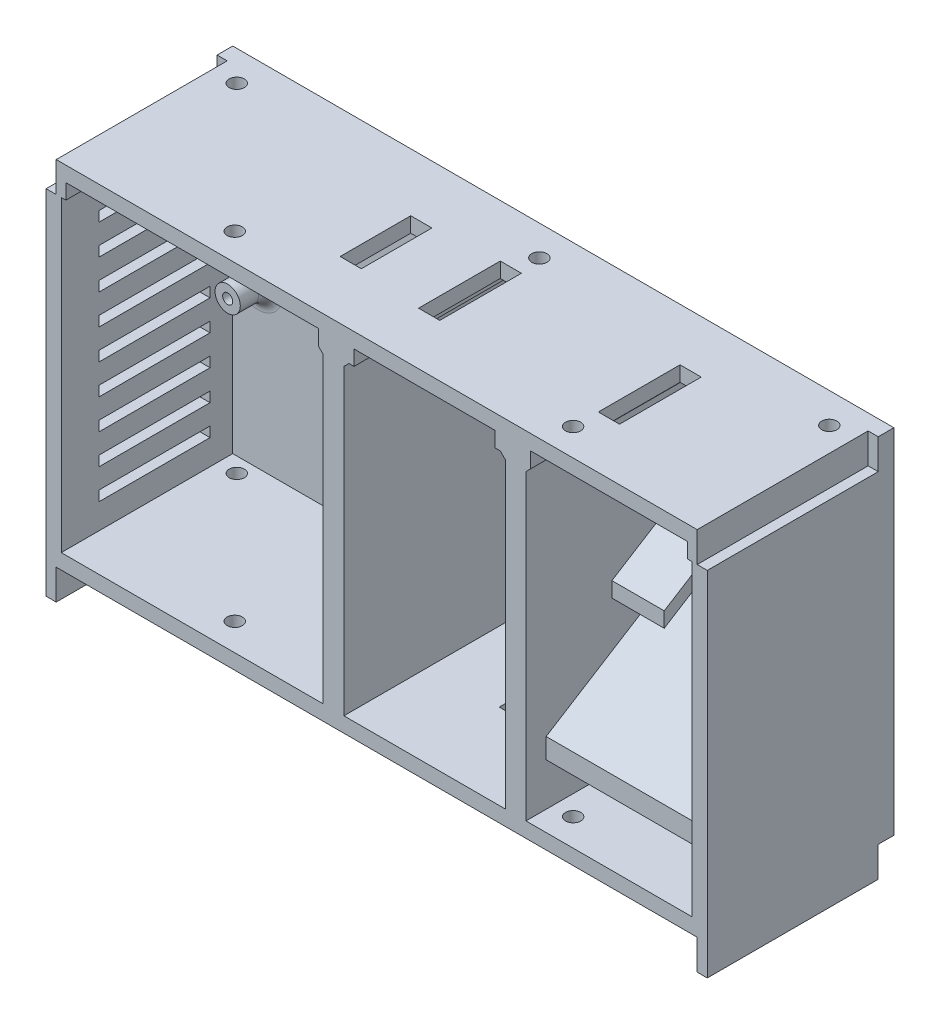
SolidWorks part; units mm, degrees
material "ABS"
ref_plane "Alzado" through (0, 0, 0) normal (0, 0, 1) x (1, 0, 0)
ref_plane "Planta" through (0, 0, 0) normal (0, 1, 0) x (1, 0, 0)
ref_plane "Vista lateral" through (0, 0, 0) normal (1, 0, 0) x (0, 0, -1)
sketch "Croquis1" plane through (0, 0, 0) normal (0, 0, 1) x (1, 0, 0)
  line L0 (0, 0) -> (2, 0)
  line L1 (2, 0) -> (2, 6)
  line L2 (55, 0) -> (55, 6)
  line L3 (55, 6) -> (2, 6)
  line L4 (56, 0) -> (56, 6)
  line L5 (56, 6) -> (58, 6)
  line L6 (58, 6) -> (58, 0)
  line L7 (58, 0) -> (59, 0)
  line L8 (59, 0) -> (59, 6)
  line L9 (91.1, 0) -> (91.1, 6)
  line L10 (59, 6) -> (91.1, 6)
  line L11 (92.1, 0) -> (92.1, 6)
  line L12 (92.1, 6) -> (94.1, 6)
  line L13 (94.1, 6) -> (94.1, 0)
  line L14 (95.1, 0) -> (95.1, 6)
  line L15 (129.1, 0) -> (129.1, 6)
  line L16 (129.1, 6) -> (95.1, 6)
  line L17 (0, 0) -> (0, -64)
  line L18 (0, -64) -> (131.1, -64)
  line L19 (131.1, -64) -> (131.1, 0)
  line L20 (55, 0) -> (56, 0)
  line L21 (58, 0) -> (59, 0)
  line L22 (129.1, 0) -> (131.1, 0)
  line L23 (94.1, 0) -> (95.1, 0)
  line L24 (91.1, 0) -> (92.1, 0)
  line L25 (2, 0) -> (129.1, 0)
  line L26 (55, 6) -> (56, 6)
  line L27 (58, 6) -> (59, 6)
  line L28 (91.1, 6) -> (92.1, 6)
  line L29 (94.1, 6) -> (95.1, 6)
  point P3 (2, 0)
  point P4 (129.1, 0)
  point P5 (55, 0)
  point P10 (56, 0)
  point P11 (58, 0)
  point P12 (59, 0)
  point P15 (91.1, 0)
  point P22 (92.1, 0)
  point P23 (94.1, 0)
  point P24 (95.1, 0)
  dimension "D1" = 131.1
  dimension "D2" = 2
  dimension "D3" = 2
  dimension "D4" = 55
  dimension "D5" = 6
  dimension "D6" = 1
  dimension "D7" = 2
  dimension "D8" = 1
  dimension "D9" = 32.1
  dimension "D10" = 1
  dimension "D11" = 2
  dimension "D12" = 1
  dimension "D13" = 64
extrude "Saliente-Extruir1" add sketch "Croquis1" along normal blind 34 contours L8 L25 L9 L10 | L1 L25 L2 L3 | L14 L25 L15 L16 | L11 L25 L13 L12 | L4 L25 L6 L5 | L26 L2 L20 L4 | L27 L6 L7 L8 | L29 L13 L23 L14 | L28 L9 L24 L11 region at (28.5, 3, 0) region at (55.5, 3, 0) region at (57, 3, 0) region at (58.5, 3, 0) region at (112.1, 3, 0) region at (75.05, 3, 0) region at (94.6, 3, 0) region at (91.6, 3, 0) region at (93.1, 3, 0)
sketch "Croquis2" plane through (0, 0, 0) normal (0, 0, 1) x (1, 0, 0)
  line L1 (2, -64) -> (129.1, -64)
  line L3 (129.1, 0) -> (2, 0)
  line L5 (129.1, 0) -> (131.1, 0)
  line L7 (129.1, -64) -> (131.1, -64)
  line L8 (131.1, 0) -> (131.1, -64)
  line L9 (2, -64) -> (0, -64)
  line L11 (2, 0) -> (0, 0)
  line L12 (0, -64) -> (0, 0)
  dimension "D1" = 64
  dimension "D2" = 2
  dimension "D3" = 2
extrude "Saliente-Extruir2" add sketch "Croquis2" along normal blind 3
sketch "Croquis3" plane through (0, 0, 3) normal (0, 0, 1) x (1, 0, 0)
  line L0 (0, -64) -> (131.1, -64) construction
  line L1 (131.1, 0) -> (128.1, 0)
  line L2 (131.1, 0) -> (131.1, -64)
  line L3 (131.1, -64) -> (128.1, -64)
  line L4 (128.1, 0) -> (128.1, -61)
  line L6 (0, 0) -> (3, 0)
  line L7 (0, 0) -> (0, -64)
  line L8 (0, -64) -> (3, -64)
  line L9 (3, 0) -> (3, -61)
  line L10 (3, -64) -> (128.1, -64)
  line L12 (3, -61) -> (128.1, -61)
  dimension "D1" = 3
  dimension "D2" = 3
  dimension "D3" = 3
extrude "Saliente-Extruir3" add sketch "Croquis3" along normal up to vertex (31 mm away) up to point (129.1, 0, 34)
sketch "Croquis4" plane through (0, 0, 0) normal (0, 0, -1) x (-1, 0, 0)
  line L25 (-2, 6) -> (-129.1, 6)
  line L34 (-129.1, 6) -> (-129.1, 0)
  line L35 (-129.1, 0) -> (-131.1, 0)
  line L36 (-131.1, 0) -> (-131.1, -64)
  line L37 (-131.1, -64) -> (0, -64)
  line L38 (0, -64) -> (0, 0)
  line L39 (0, 0) -> (-2, 0)
  line L40 (-2, 0) -> (-2, 6)
  line L49 (-2, 6) -> (-129.1, 6)
  line L58 (-129.1, 6) -> (-129.1, 0)
  line L59 (-129.1, 0) -> (-131.1, 0)
  line L60 (-131.1, 0) -> (-131.1, -64)
  line L61 (-131.1, -64) -> (0, -64)
  line L62 (0, -64) -> (0, 0)
  line L63 (0, 0) -> (-2, 0)
  line L64 (-2, 0) -> (-2, 6)
  dimension "D1" = 0
extrude "Saliente-Extruir4" add sketch "Croquis4" along normal blind 3
sketch "Croquis5" plane through (0, 0, 3) normal (0, 0, 1) x (1, 0, 0)
  line L1 (128.1, -61) -> (3, -61) construction
  line L4 (0, -64) -> (0, 0) construction
  line L23 (54.95, 0.05) -> (59.05, 0.05)
  line L26 (128.1, 0) -> (3, 0) construction
  line L27 (54.95, 0.05) -> (54.95, -61)
  line L28 (59.05, 0.05) -> (59.05, -61)
  line L29 (91.05, 0.05) -> (95.15, 0.05)
  line L32 (196.65, 0) -> (-65.55, 0) construction
  line L33 (91.05, 0.05) -> (91.05, -61)
  line L34 (128.1, -61) -> (3, -61) construction
  line L35 (91.05, -61) -> (95.15, -61)
  line L36 (95.15, -61) -> (95.15, 0.05)
  line M6 (128.1, 0) -> (3, 0)
  line M8 (128.1, 0) -> (3, 0)
  line M10 (128.1, 0) -> (3, 0)
  line M12 (128.1, 0) -> (3, 0)
  line M14 (128.1, 0) -> (3, 0)
  line M16 (3, -61) -> (128.1, -61)
  dimension "D1" = 54.95
  dimension "D2" = 32
  dimension "D3" = 4.1
  dimension "D4" = 0.05
  dimension "D6" = 0.05
extrude "Saliente-Extruir10" add sketch "Croquis5" along normal up to vertex (31 mm away) contours L28 L27 M10 M12 M14 M16 | L36 L33 M16 M6 M8 M10 region at (57, -30.5, 3) region at (93.1, -30.5, 3) up to point (3, 0, 34)
sketch "Croquis6" plane through (0, 0, 0) normal (0, -1, 0) x (1, 0, 0)
  line L0 (0, 34) -> (0, -3) construction
  line L1 (0, 15.5) -> (131.1, 15.5) construction
  line L2 (131.1, 34) -> (131.1, -3) construction
  line L3 (51, 8.5) -> (51, 22.5)
  line L4 (51, 22.5) -> (46.8, 22.5)
  line L5 (46.8, 22.5) -> (46.8, 8.5)
  line L6 (46.8, 8.5) -> (51, 8.5)
  line L7 (99.1, 7.4) -> (99.1, 23.6)
  line L8 (99.1, 23.6) -> (103.3, 23.6)
  line L9 (103.3, 23.6) -> (103.3, 7.4)
  line L10 (103.3, 7.4) -> (99.1, 7.4)
  line L11 (63.45, 7.4) -> (63.45, 23.6)
  line L12 (63.45, 23.6) -> (67.65, 23.6)
  line L13 (67.65, 23.6) -> (67.65, 7.4)
  line L14 (67.65, 7.4) -> (63.45, 7.4)
  point P6 (99.1, 15.5)
  point P9 (51, 15.5)
  point P15 (99.1, 15.5)
  point P17 (63.45, 15.5)
  point P21 (63.45, 15.5)
  dimension "D1" = 51
  dimension "D2" = 4.2
  dimension "D3" = 14
  dimension "D4" = 32
  dimension "D5" = 16.2
  dimension "D6" = 4.2
  dimension "D7" = 12.45
extrude "Cortar-Extruir1" cut sketch "Croquis6" against normal up to next
sketch "Croquis7" plane through (0, 0, 34) normal (0, 0, 1) x (1, 0, 0)
  line L0 (3, 0) -> (54.95, 0) construction
  line L1 (28.975, 0) -> (28.975, 3)
  line L2 (3.925, 3) -> (54.025, 3)
  line L3 (54.025, 3) -> (54.025, 0)
  line L4 (3.925, 0) -> (54.025, 0)
  line L5 (3.925, 3) -> (3.925, 0)
  line L6 (75.05, 0) -> (75.05, 3)
  line L7 (59.05, 0) -> (91.05, 0) construction
  line L8 (75.05, 3) -> (89.05, 3)
  line L9 (89.05, 3) -> (89.05, 0)
  line L10 (89.05, 0) -> (75.05, 0)
  line L11 (75.05, 3) -> (61.05, 3)
  line L12 (61.05, 3) -> (61.05, 0)
  line L13 (61.05, 0) -> (75.05, 0)
  line L14 (61.05, 3) -> (75.05, 3)
  line L15 (111.625, 0) -> (111.625, 3)
  line L16 (95.15, 0) -> (128.1, 0) construction
  line L17 (111.625, 3) -> (127.225, 3)
  line L18 (127.225, 3) -> (127.225, 0)
  line L19 (127.225, 0) -> (111.625, 0)
  line L20 (111.625, 0) -> (96.025, 0)
  line L21 (96.025, 0) -> (96.025, 3)
  line L22 (96.025, 3) -> (111.625, 3)
  line M5 (59.05, 0) -> (91.05, 0)
  line M10 (95.15, 0) -> (128.1, 0)
  line M37 (3, 0) -> (54.95, 0)
  dimension "D1" = 25.05
  dimension "D2" = 3
  dimension "D3" = 14
  dimension "D4" = 15.6
extrude "Cortar-Extruir2" cut sketch "Croquis7" against normal up to vertex (31 mm away) contours L3 L2 L1 M37 | L2 L5 L1 M37 | L11 L12 L6 M5 | L9 L8 L6 M5 | L22 L21 L15 M10 | L18 L17 L15 M10 region at (16.45, 1.5, 34) region at (41.5, 1.5, 34) region at (68.05, 1.5, 34) region at (82.05, 1.5, 34) region at (103.825, 1.5, 34) region at (119.425, 1.5, 34) up to point (95.15, 0, 3)
sketch "Croquis22" plane through (0, 0, 3) normal (0, 0, 1) x (1, 0, 0)
  line L0 (95.15, 0) -> (95.15, -61) construction
  line L1 (95.15, -61) -> (128.1, -61) construction
  line L2 (128.1, -61) -> (128.1, 0) construction
  line L3 (128.1, 0) -> (127.225, 0) construction
  line L4 (127.225, 0) -> (127.225, 3) construction
  line L5 (127.225, 3) -> (96.025, 3) construction
  line L6 (96.025, 3) -> (96.025, 0) construction
  line L7 (96.025, 0) -> (95.15, 0) construction
  line L8 (91.05, -61) -> (91.05, 0) construction
  line L9 (91.05, 0) -> (89.05, 0) construction
  line L10 (89.05, 0) -> (89.05, 3) construction
  line L11 (89.05, 3) -> (61.05, 3) construction
  line L12 (61.05, 3) -> (61.05, 0) construction
  line L13 (61.05, 0) -> (59.05, 0) construction
  line L14 (59.05, 0) -> (59.05, -61) construction
  line L15 (59.05, -61) -> (91.05, -61) construction
  line L16 (54.95, -61) -> (54.95, 0) construction
  line L17 (54.95, 0) -> (54.025, 0) construction
  line L18 (54.025, 0) -> (54.025, 3) construction
  line L19 (54.025, 3) -> (3.925, 3) construction
  line L20 (3.925, 3) -> (3.925, 0) construction
  line L21 (3.925, 0) -> (3, 0) construction
  line L22 (3, 0) -> (3, -61) construction
  line L23 (3, -61) -> (54.95, -61) construction
  line L24 (95.15, 0) -> (95.15, -61)
  line L25 (95.15, -61) -> (128.1, -61)
  line L26 (128.1, -61) -> (128.1, 0)
  line L27 (128.1, 0) -> (127.225, 0)
  line L28 (127.225, 0) -> (127.225, 3)
  line L29 (127.225, 3) -> (96.025, 3)
  line L30 (96.025, 3) -> (96.025, 0)
  line L31 (96.025, 0) -> (95.15, 0)
  line L32 (91.05, -61) -> (91.05, 0)
  line L33 (91.05, 0) -> (89.05, 0)
  line L34 (89.05, 0) -> (89.05, 3)
  line L35 (89.05, 3) -> (61.05, 3)
  line L36 (61.05, 3) -> (61.05, 0)
  line L37 (61.05, 0) -> (59.05, 0)
  line L38 (59.05, 0) -> (59.05, -61)
  line L39 (59.05, -61) -> (91.05, -61)
  line L40 (54.95, -61) -> (54.95, 0)
  line L41 (54.95, 0) -> (54.025, 0)
  line L42 (54.025, 0) -> (54.025, 3)
  line L43 (54.025, 3) -> (3.925, 3)
  line L44 (3.925, 3) -> (3.925, 0)
  line L45 (3.925, 0) -> (3, 0)
  line L46 (3, 0) -> (3, -61)
  line L47 (3, -61) -> (54.95, -61)
extrude "Cortar-Extruir8" cut sketch "Croquis22" against normal blind 3 contours L40 L41 L42 L43 L44 L45 L46 L47 | L32 L33 L34 L35 L36 L37 L38 L39 | L24 L25 L26 L27 L28 L29 L30 L31
sketch "Croquis24" plane through (2, 0, 0) normal (-1, 0, 0) x (0, 0, 1)
  line L0 (34, 0) -> (-3, 0) construction
  line L5 (0.1, 0) -> (-4.3164, 0)
  line L6 (0.1, 0) -> (0.1, 6.5451)
  line L7 (0.1, 6.5451) -> (-4.3164, 6.5451)
  line L8 (-4.3164, 0) -> (-4.3164, 6.5451)
  line L9 (0, 0) -> (0, 8.0802) construction
  dimension "D1" = 0.1
extrude "Cortar-Extruir11" cut sketch "Croquis24" against normal through all contours L6 L5 L8 L7
sketch "Croquis26" plane through (0, 0, 0) normal (0, 0, 1) x (1, 0, 0)
  line L0 (4, -60) -> (54.1, -60)
  line L1 (4, -60) -> (4, -4.1)
  line L2 (4, -4.1) -> (54.1, -4.1)
  line L3 (54.1, -60) -> (54.1, -4.1)
  line L4 (4, -60) -> (54.1, -4.1) construction
  line L5 (4, -4.1) -> (54.1, -60) construction
  line L6 (36.1, -45) -> (46.1, -45)
  line L7 (36.1, -45) -> (36.1, -39)
  line L8 (36.1, -39) -> (46.1, -39)
  line L9 (46.1, -45) -> (46.1, -39)
  line L10 (3, -61) -> (54.95, -61) construction
  line L11 (3, 0) -> (3, -61) construction
  line L12 (54.95, -61) -> (54.95, 0) construction
  circle A0 centre (24, -8.1) radius 1
  circle A1 centre (8, -28.9) radius 1
  circle A2 centre (24, -8.1) radius 2.5
  circle A3 centre (8, -28.9) radius 2.5
  point P0 (29.05, -32.05)
  point P5 (24, -8.1)
  point P8 (8, -28.9)
  dimension "D6" = 2
  dimension "D7" = 5
  dimension "D1" = 1
  dimension "D2" = 55.9
  dimension "D3" = 1
  dimension "D4" = 4
  dimension "D5" = 24.8
  dimension "D8" = 4
  dimension "D9" = 20
  dimension "D10" = 8
  dimension "D11" = 15
  dimension "D12" = 6
  dimension "D13" = 10
  dimension "D14" = 0.85
extrude "Saliente-Extruir16" add sketch "Croquis26" along normal blind 6 contours L6 L9 L8 L7 | A2 A0 | A3 A1 region at (41.1, -42, 0) region at (21.5707, -8.1, 0) region at (5.5707, -28.9, 0)
fillet "Redondeo1" radius 2.4 3 edges at (10.5, -28.9, 0) (26.5, -8.1, 0) (46.1, -42, 0)
chamfer "Chaflán1" distance 1 angle 45 4 edges at (54.95, 0, 17.05) (95.15, 0, 17.05) (91.05, 0, 17.05) (59.05, 0, 17.05)
sketch "Croquis10" plane through (0, 0, 0) normal (-1, 0, 0) x (0, 0, 1)
  line L0 (15.5, -64) -> (15.5, 6) construction
  line L1 (34, -64) -> (-3, -64) construction
  line L3 (4.5, -50) -> (4.5, -48)
  line L4 (4.5, -56) -> (26.5, -56)
  line L5 (4.5, -56) -> (4.5, -54)
  line L6 (4.5, -54) -> (26.5, -54)
  line L7 (26.5, -56) -> (26.5, -54)
  line L8 (4.5, -56) -> (26.5, -54) construction
  line L9 (4.5, -54) -> (26.5, -56) construction
  line L10 (4.5, -50) -> (26.5, -50)
  line L11 (26.5, -50) -> (26.5, -48)
  line L12 (4.5, -48) -> (26.5, -48)
  line L13 (4.5, -44) -> (4.5, -42)
  line L14 (4.5, -44) -> (26.5, -44)
  line L15 (26.5, -44) -> (26.5, -42)
  line L16 (4.5, -42) -> (26.5, -42)
  line L17 (4.5, -38) -> (4.5, -36)
  line L18 (4.5, -38) -> (26.5, -38)
  line L19 (26.5, -38) -> (26.5, -36)
  line L20 (4.5, -36) -> (26.5, -36)
  line L21 (4.5, -32) -> (4.5, -30)
  line L22 (4.5, -32) -> (26.5, -32)
  line L23 (26.5, -32) -> (26.5, -30)
  line L24 (4.5, -30) -> (26.5, -30)
  line L25 (4.5, -26) -> (4.5, -24)
  line L26 (4.5, -26) -> (26.5, -26)
  line L27 (26.5, -26) -> (26.5, -24)
  line L28 (4.5, -24) -> (26.5, -24)
  line L29 (4.5, -20) -> (4.5, -18)
  line L30 (4.5, -20) -> (26.5, -20)
  line L31 (26.5, -20) -> (26.5, -18)
  line L32 (4.5, -18) -> (26.5, -18)
  line L33 (4.5, -14) -> (4.5, -12)
  line L34 (4.5, -14) -> (26.5, -14)
  line L35 (26.5, -14) -> (26.5, -12)
  line L36 (4.5, -12) -> (26.5, -12)
  line L37 (4.5, -8) -> (4.5, -6)
  line L38 (4.5, -8) -> (26.5, -8)
  line L39 (26.5, -8) -> (26.5, -6)
  line L40 (4.5, -6) -> (26.5, -6)
  point P6 (15.5, -55)
  dimension "D1" = 22
  dimension "D2" = 2
  dimension "D3" = 8
  dimension "D4" = 9
extrude "Cortar-Extruir3" cut sketch "Croquis10" against normal up to vertex (3 mm away) contours L4 L7 L6 L5 | L12 L3 L10 L11 | L16 L13 L14 L15 | L20 L17 L18 L19 | L24 L21 L22 L23 | L28 L25 L26 L27 | L32 L29 L30 L31 | L36 L33 L34 L35 | L40 L37 L38 L39 region at (0, -49, 15.5) region at (0, -55, 15.5) region at (0, -43, 15.5) region at (0, -37, 15.5) region at (0, -31, 15.5) region at (0, -25, 15.5) region at (0, -19, 15.5) region at (0, -13, 15.5) region at (0, -7, 15.5) up to point (3, -61, 34)
sketch "Croquis12" plane through (95.15, 0, 0) normal (1, 0, 0) x (0, 0, -1)
  line L0 (0, -29.7544) -> (-34, -51)
  line L1 (0, 0) -> (0, -61) construction
  line L2 (-34, -61) -> (-34, -1) construction
  line L4 (-34, -51) -> (-34, -55)
  line L5 (-34, -55) -> (0, -33.7544)
  line L6 (0, -29.7544) -> (0, -33.7544)
  dimension "D1" = 4
  dimension "D2" = 58
  dimension "D3" = 6
extrude "Saliente-Extruir12" add sketch "Croquis12" along normal up to surface (32.95 mm away) up to face at (128.1, -24.4, 13.62)
sketch "Croquis13" plane through (95.15, 0, 0) normal (1, 0, 0) x (0, 0, -1)
  line L0 (0, -29.7544) -> (0, -20.6544) construction
  line L2 (0, -20.6544) -> (-16.961, -31.2528)
  line L4 (0, -29.7544) -> (-34, -51) construction
  line L6 (-16.961, -28.2528) -> (0, -17.6544)
  line L7 (0, -17.6544) -> (0, -20.6544)
  line L8 (-16.961, -31.2528) -> (-16.961, -28.2528)
  line L9 (-34, -51) -> (-8.7351, -35.2127) construction
  line L10 (0, -29.7544) -> (-34, -51) construction
  line L11 (-4.2402, -32.404) -> (-4.2402, -23.304)
  line L12 (-4.2402, -32.404) -> (0, -29.7544)
  line L13 (0, 0) -> (0, -29.7544) construction
  line M8 (-34, -51) -> (0, -29.7544)
  line M18 (0, -29.7544) -> (0, 0)
  dimension "D1" = 9.1
  dimension "D2" = 3
  dimension "D3" = 20
  dimension "D4" = 5
extrude "Saliente-Extruir17" add sketch "Croquis13" along normal up to surface (32.95 mm away) contours L11 L2 M8 M18 | L8 L2 L6 M18 region at (95.15, -26.5292, 2.1201) region at (95.15, -24.4536, 8.4805) up to face at (128.1, -52.6886, 17)
ref_plane "Plano1" through (0, -17.6544, 0) normal (0, -1, 0) x (-1, 0, 0)
sketch "Croquis38" plane through (0, -17.6544, 0) normal (0, -1, 0) x (-1, 0, 0)
  line L0 (-111.625, 0) -> (-111.625, -34.0311) construction
  line L1 (-128.1, 0) -> (-95.15, 0) construction
  line L2 (-111.625, 0) -> (-117.725, 0)
  line L3 (-117.725, 0) -> (-117.725, -26)
  line L4 (-117.725, -26) -> (-105.525, -26)
  line L5 (-111.625, 0) -> (-105.525, 0)
  line L6 (-105.525, 0) -> (-105.525, -26)
  dimension "D1" = 6.1
  dimension "D2" = 6.1
  dimension "D3" = 26
  dimension "D4" = 26
extrude "Cortar-Extruir12" cut sketch "Croquis38" along normal up to vertex (14.7496 mm away) contours L0 L2 L3 L4 | L5 L0 L4 L6 region at (108.575, -17.6544, 13) region at (114.675, -17.6544, 13) up to point (128.1, -32.404, 4.2402)
sketch "Croquis40" plane through (0, 3, 0) normal (0, -1, 0) x (1, 0, 0)
  line L0 (0, 34) -> (0, -3) construction
  line L1 (3.925, 34) -> (54.025, 34) construction
  line L2 (131.1, 34) -> (131.1, -3) construction
  line L3 (0, -3) -> (131.1, -3) construction
  circle A0 centre (32, 28.6) radius 1.5
  circle A1 centre (99.1, 28.6) radius 1.5
  circle A2 centre (6.8, 3) radius 1.5
  circle A3 centre (124.3, 3) radius 1.5
  circle A4 centre (66.8, 3) radius 1.5
  dimension "D3" = 3
  dimension "D1" = 32
  dimension "D2" = 5.4
  dimension "D4" = 32
  dimension "D5" = 6.8
  dimension "D6" = 6
  dimension "D7" = 6.8
  dimension "D8" = 60
extrude "Cortar-Extruir13" cut sketch "Croquis40" against normal up to next
sketch "Croquis48" plane through (0, 0, 0) normal (-1, 0, 0) x (0, 0, 1)
  line L1 (-3, 0) -> (0.1, 0)
  line L2 (-3, 0) -> (-3, 6)
  line L3 (-3, 6) -> (0.1, 6)
  line L4 (0.1, 0) -> (0.1, 6)
extrude "Saliente-Extruir20" add sketch "Croquis48" against normal up to vertex (131.1 mm away) up to point (131.1, 0, -3)
sketch "Croquis49" plane through (0, 0, 34) normal (0, 0, 1) x (1, 0, 0)
  line L0 (2, 0) -> (2, -64) construction
  line L1 (0, -64) -> (131.1, -64) construction
  line L2 (129.1, 0) -> (129.1, -64) construction
  line L4 (2, -64) -> (0, -64)
  line L5 (0, -64) -> (0, -70)
  line L6 (0, -70) -> (2, -70)
  line L7 (2, -70) -> (2, -64)
  line L8 (129.1, -64) -> (131.1, -64)
  line L9 (131.1, -64) -> (131.1, -70)
  line L10 (131.1, -70) -> (129.1, -70)
  line L11 (129.1, -70) -> (129.1, -64)
  line L12 (65.55, -64) -> (68.55, -64)
  line L16 (62.55, -64) -> (65.55, -64)
  dimension "D1" = 6
  dimension "D2" = 3
extrude "Saliente-Extruir21" add sketch "Croquis49" against normal up to vertex (33.9 mm away) contours L6 L7 L4 L5 | L16 | L12 | L11 L10 L9 L8 region at (1, -67, 34) region at (130.1, -67, 34) up to point (2, 0, 0.1)
sketch "Croquis50" plane through (0, -64, 0) normal (0, -1, 0) x (1, 0, 0)
  circle A0 centre (124.3, 3) radius 1.5 construction
  circle A1 centre (99.1, 28.6) radius 1.5 construction
  circle A3 centre (6.8, 3) radius 1.5 construction
  circle A4 centre (32, 28.6) radius 1.5 construction
  circle A5 centre (124.3, 3) radius 1.5
  circle A6 centre (99.1, 28.6) radius 1.5
  circle A8 centre (6.8, 3) radius 1.5
  circle A9 centre (32, 28.6) radius 1.5
extrude "Cortar-Extruir14" cut sketch "Croquis50" against normal up to surface (3 mm away) up to face at (28.975, -61, 17)
sketch "Croquis51" plane through (0, 0, 0) normal (-1, 0, 0) x (0, 0, 1)
  line L0 (0.1, -64) -> (-3, -64) construction
  line L1 (-3, 6) -> (-2.9, 6)
  line L2 (-3, 6) -> (-3, -64)
  line L3 (-3, -64) -> (-2.9, -64)
  line L4 (-2.9, 6) -> (-2.9, -64)
  dimension "D1" = 0.1
extrude "Cortar-Extruir15" cut sketch "Croquis51" against normal through all
sketch "Croquis52" plane through (0, -64, 0) normal (0, -1, 0) x (1, 0, 0)
  line L1 (72.95, 17.1) -> (78.95, 17.1)
  line L2 (72.95, 17.1) -> (72.95, 9.1)
  line L3 (72.95, 9.1) -> (78.95, 9.1)
  line L4 (78.95, 17.1) -> (78.95, 9.1)
  line L5 (131.1, -2.9) -> (0, -2.9) construction
  line L6 (0, 0.1) -> (0, 34) construction
  dimension "D2" = 12
  dimension "D3" = 8
  dimension "D4" = 6
  dimension "D5" = 72.95
extrude "Cortar-Extruir16" cut sketch "Croquis52" against normal up to vertex (3 mm away) up to point (59.05, -61, 34)
sketch "Croquis53" plane through (0, 0, 34) normal (0, 0, 1) x (1, 0, 0)
  line L0 (128.1, 0) -> (128.1, -51) construction
  line L1 (95.15, -51) -> (128.1, -51)
  line L2 (95.15, -51) -> (95.15, -55)
  line L3 (95.15, -55) -> (128.1, -55)
  line L4 (128.1, -51) -> (128.1, -55)
  line L5 (95.15, -51) -> (128.1, -51)
  line L6 (95.15, -51) -> (95.15, -48.3278)
  line L7 (95.15, -48.3278) -> (128.1, -48.3278)
  line L8 (128.1, -51) -> (128.1, -48.3278)
extrude "Cortar-Extruir17" cut sketch "Croquis53" against normal blind 4 contours L4 L1 L2 L3 | L1 L8 L7 L6 region at (111.625, -49.6639, 34) region at (111.625, -53, 34)
sketch "Croquis54" plane through (0, 0, -2.9) normal (0, 0, -1) x (-1, 0, 0)
  line L1 (-131.1, 6) -> (0, 6)
  line L2 (-131.1, 6) -> (-131.1, -64)
  line L3 (-131.1, -64) -> (0, -64)
  line L4 (0, 6) -> (0, -64)
extrude "Saliente-Extruir22" add sketch "Croquis54" along normal blind 0.1
sketch "Croquis55" plane through (0, 0, 0) normal (0, 0, 1) x (1, 0, 0)
  line L0 (91.05, -61) -> (59.05, -61) construction
  line L1 (59.05, 0) -> (59.05, -61) construction
  circle A0 centre (65.25, -56.4) radius 1.1
  circle A1 centre (83.95, -56.4) radius 1.1
  circle A2 centre (83.95, -27) radius 1.1
  circle A3 centre (65.25, -27) radius 1.1
  circle A4 centre (65.25, -27) radius 2.2
  circle A5 centre (83.95, -27) radius 2.2
  circle A6 centre (83.95, -56.4) radius 2.2
  circle A7 centre (65.25, -56.4) radius 2.2
  dimension "D1" = 18.7
  dimension "D2" = 29.4
  dimension "D3" = 2.2
  dimension "D6" = 4.4
  dimension "D4" = 4.6
  dimension "D5" = 6.2
extrude "Saliente-Extruir23" add sketch "Croquis55" along normal blind 5
fillet "Redondeo2" radius 2.56 4 edges at (67.45, -56.4, 0) (86.15, -56.4, 0) (86.15, -27, 0) (67.45, -27, 0)
